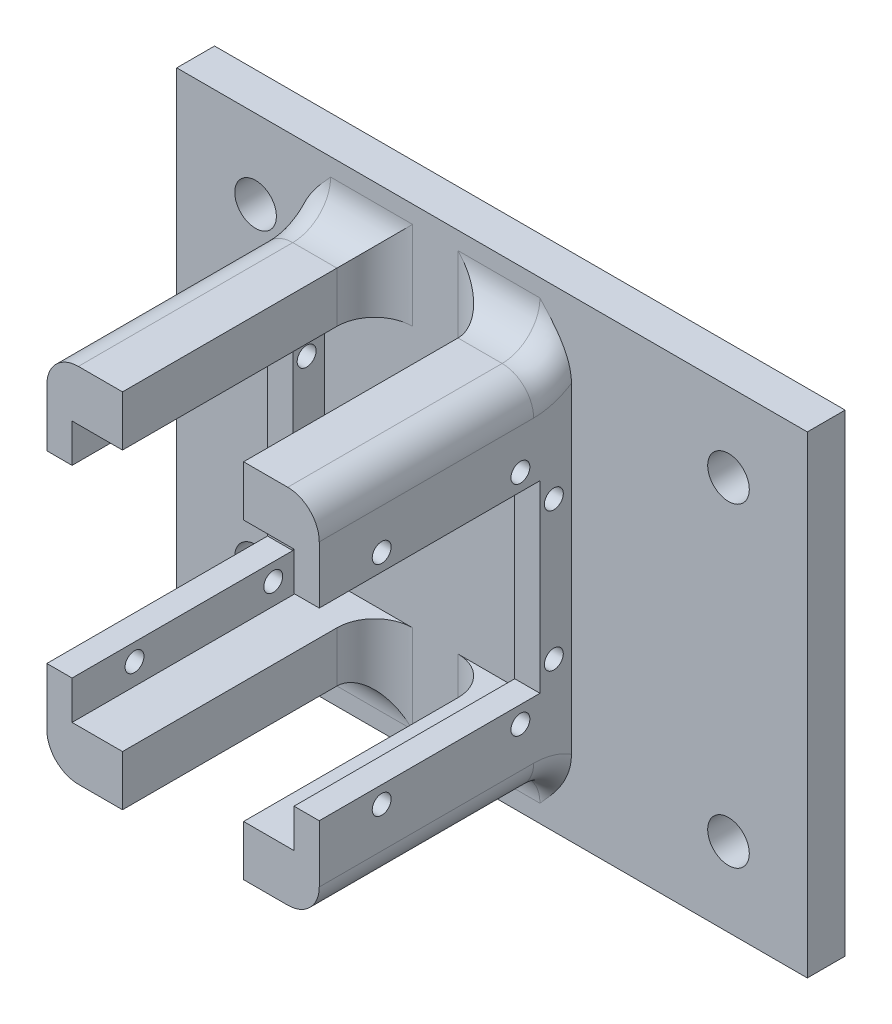
SolidWorks part; units mm, degrees
ref_plane "정면" through (0, 0, 0) normal (0, 0, 1) x (1, 0, 0)
ref_plane "윗면" through (0, 0, 0) normal (0, 1, 0) x (1, 0, 0)
ref_plane "우측면" through (0, 0, 0) normal (1, 0, 0) x (0, 0, -1)
sketch "스케치1" plane through (0, 0, 0) normal (0, 0, 1) x (1, 0, 0)
  line L1 (50, -37.5) -> (-50, -37.5)
  line L2 (50, -37.5) -> (50, 37.5)
  line L3 (50, 37.5) -> (-50, 37.5)
  line L4 (-50, -37.5) -> (-50, 37.5)
  line L5 (50, -37.5) -> (-50, 37.5) construction
  line L6 (50, 37.5) -> (-50, -37.5) construction
  line L7 (37.5, -25) -> (-37.5, -25) construction
  line L8 (37.5, -25) -> (37.5, 25) construction
  line L9 (37.5, 25) -> (-37.5, 25) construction
  line L10 (-37.5, -25) -> (-37.5, 25) construction
  line L11 (37.5, -25) -> (-37.5, 25) construction
  line L12 (37.5, 25) -> (-37.5, -25) construction
  circle A0 centre (-37.5, 25) radius 3.3
  circle A1 centre (37.5, 25) radius 3.3
  circle A2 centre (37.5, -25) radius 3.3
  circle A3 centre (-37.5, -25) radius 3.3
  point P0 (0, 0)
  point P6 (0, 0)
  dimension "D5" = 6.6
  dimension "D1" = 75
  dimension "D2" = 100
  dimension "D3" = 50
  dimension "D4" = 75
extrude "보스-돌출1" add sketch "스케치1" along normal blind 6
sketch "스케치2" plane through (0, 0, 6) normal (0, 0, 1) x (1, 0, 0)
  line L0 (-37.5, 25) -> (-37.5, -25) construction
  line L3 (-32.5, 37.5) -> (-32.5, -37.5) construction
  line L4 (50, 37.5) -> (-50, 37.5) construction
  line L5 (-50, -37.5) -> (50, -37.5) construction
  line L6 (-29.5, 37.5) -> (-29.5, -37.5) construction
  line L7 (-50, 0) -> (50, 0) construction
  line L8 (-50, 37.5) -> (-50, -37.5) construction
  line L9 (50, -37.5) -> (50, 37.5) construction
  line L10 (-50, 14.5) -> (50, 14.5) construction
  line L11 (-50, 17.3) -> (50, 17.3) construction
  line L12 (-50, 18.8) -> (50, 18.8) construction
  line L13 (-50, 20.1) -> (50, 20.1) construction
  line L14 (-18.6, 20.7) -> (-18.6, 28.7)
  line L15 (8, -20.1) -> (-26, -20.1) construction
  line L16 (8, -20.1) -> (8, 20.1) construction
  line L17 (8, 20.1) -> (-26, 20.1) construction
  line L18 (-26, -20.1) -> (-26, 20.1) construction
  line L19 (8, -20.1) -> (-26, 20.1) construction
  line L20 (8, 20.1) -> (-26, -20.1) construction
  line L21 (-18.6, 28.7) -> (-30.6, 28.7)
  line L22 (-30.6, 28.7) -> (-30.6, -28.7)
  line L23 (-26.6, -20.7) -> (-18.6, -20.7)
  line L24 (-26.6, -20.7) -> (-26.6, 20.7)
  line L25 (-26.6, 20.7) -> (-18.6, 20.7)
  line L26 (-18.6, -20.7) -> (-18.6, -28.7)
  line L27 (-18.6, -28.7) -> (-30.6, -28.7)
  line L28 (-9, 20.1) -> (-9, -20.1) construction
  line L29 (8.6, -20.7) -> (0.6, -20.7)
  line L30 (0.6, -20.7) -> (0.6, -28.7)
  line L31 (0.6, -28.7) -> (12.6, -28.7)
  line L32 (12.6, 28.7) -> (12.6, -28.7)
  line L33 (8.6, -20.7) -> (8.6, 20.7)
  line L34 (8.6, 20.7) -> (0.6, 20.7)
  line L35 (0.6, 20.7) -> (0.6, 28.7)
  line L36 (0.6, 28.7) -> (12.6, 28.7)
  point P26 (-9, 0)
  point P38 (-26.6, 0)
  point P41 (-30.6, 0)
  dimension "D1" = 5
  dimension "D2" = 3
  dimension "D3" = 14.5
  dimension "D4" = 17.3
  dimension "D5" = 1.5
  dimension "D6" = 20.1
  dimension "D7" = 3.5
  dimension "D8" = 34
  dimension "D9" = 0.6
  dimension "D10" = 0.6
  dimension "D11" = 8
  dimension "D12" = 4
  dimension "D13" = 12
extrude "보스-돌출2" add sketch "스케치2" along normal blind 40
sketch "스케치3" plane through (-30.6, 0, 0) normal (-1, 0, 0) x (0, 0, 1)
  line L0 (46, 28.7) -> (46, -28.7) construction
  line L1 (11, -14.6) -> (46, -14.6)
  line L2 (11, -14.6) -> (11, 14.6)
  line L3 (11, 14.6) -> (46, 14.6)
  line L4 (46, -14.6) -> (46, 14.6)
  line L5 (11, -14.6) -> (46, 14.6) construction
  line L6 (11, 14.6) -> (46, -14.6) construction
  line L7 (6, 28.7) -> (6, -28.7) construction
  line L8 (0, 0) -> (46, 0) construction
  line L9 (6, 37.5) -> (6, -37.5) construction
  circle A0 centre (8.8, 11) radius 1.5
  circle A1 centre (14.1, 17.3) radius 1.5
  circle A2 centre (36.1, 17.3) radius 1.5
  circle A3 centre (8.8, -11) radius 1.5
  circle A4 centre (14.1, -17.3) radius 1.5
  circle A5 centre (36.1, -17.3) radius 1.5
  point P0 (28.5, 0)
  point P20 (0, 0)
  dimension "D3" = 3
  dimension "D1" = 5
  dimension "D2" = 14.6
  dimension "D4" = 2.8
  dimension "D5" = 11
  dimension "D6" = 17.3
  dimension "D7" = 8.1
  dimension "D8" = 22
extrude "컷-돌출1" cut sketch "스케치3" against normal up to surface (43.2 mm away) up to face at (12.6, 0, 26)
fillet "필렛1" radius 6 8 edges at (-24.6, 28.7, 6) (-18.6, 24.7, 6) (0.6, 24.7, 6) (6.6, 28.7, 6) (6.6, -28.7, 6) (0.6, -24.7, 6) (-18.6, -24.7, 6) (-24.6, -28.7, 6)
fillet "필렛2" radius 5 8 edges at (-30.6, 30.4574, 7.7574) (12.6, 30.4574, 7.7574) (-30.6, -30.4574, 7.7574) (12.6, -30.4574, 7.7574) (-30.6, 28.7, 29) (12.6, 28.7, 29) (-30.6, -28.7, 29) (12.6, -28.7, 29)
